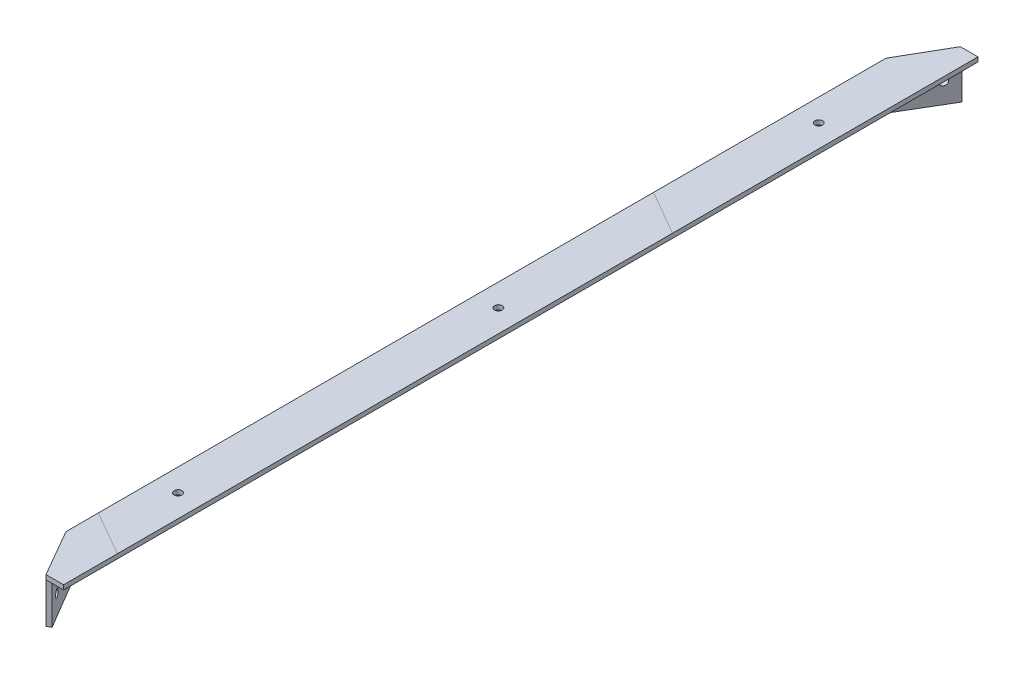
SolidWorks part; units mm, degrees
material "1.0116 (S235J2G3)"
ref_plane "Front Plane" through (0, 0, 0) normal (0, 0, 1) x (1, 0, 0)
ref_plane "Top Plane" through (0, 0, 0) normal (0, 1, 0) x (1, 0, 0)
ref_plane "Right Plane" through (0, 0, 0) normal (1, 0, 0) x (0, 0, -1)
sketch "Sketch1" plane through (0, 0, 0) normal (0, 0, 1) x (1, 0, 0)
  line L6 (0, 0) -> (0, 70)
  line L7 (0, 70) -> (70, 70)
  line L8 (70, 70) -> (70, 63)
  line L9 (70, 63) -> (7, 63)
  line L10 (7, 63) -> (7, 0)
  line L11 (7, 0) -> (0, 0)
  dimension "D1" = 70
  dimension "D2" = 70
  dimension "D3" = 7
  dimension "D4" = 7
extrude "Boss-Extrude1" add sketch "Sketch1" along normal blind 640
sketch "Sketch21" plane through (0, 0, 0) normal (0, 0, -1) x (-1, 0, 0)
  line L0 (0, 70) -> (-70, 70) construction
  line L1 (-70, 70) -> (-70, 0) construction
  line L2 (-70, 0) -> (0, 0) construction
  line L3 (0, 0) -> (0, 69.2595) construction
sketch "Sketch22" plane through (0, 70, 0) normal (0, 1, 0) x (1, 0, 0)
  line L0 (70, 0) -> (0, 0) construction
  line L1 (0, -55) -> (0, 55) construction
  circle A0 centre (35, 0) radius 6
  circle A1 centre (35, 500) radius 6
  circle A2 centre (35, -500) radius 6
  dimension "D1" = 12
  dimension "D2" = 12
  dimension "D3" = 12
  dimension "D4" = 500
  dimension "D5" = 500
  dimension "D6" = 35
  dimension "D7" = 35
extrude "Cut-Extrude4" cut sketch "Sketch22" against normal blind 10
sketch "Sketch23" plane through (0, 0, 0) normal (0, 1, 0) x (1, 0, 0)
  line L0 (0, -640) -> (42.5, -713.6122)
  line L1 (42.5, -713.6122) -> (48.5622, -710.1122)
  line L2 (48.5622, -710.1122) -> (7, -640)
  line L3 (7, -640) -> (0, -640)
  line L4 (0, -55) -> (0, 55) construction
  dimension "D1" = 7
  dimension "D2" = 210
  dimension "D3" = 85
extrude "Boss-Extrude2" add sketch "Sketch23" along normal blind 63
sketch "Sketch25" plane through (0, 63, 0) normal (0, 1, 0) x (1, 0, 0)
  line L0 (70, -640) -> (0, -640)
  line L1 (70, -640) -> (70, 0) construction
  line L2 (7, -640) -> (70, -640) construction
  line L3 (0, -640) -> (42.5, -713.6122) construction
  line L4 (0, -640) -> (42.5, -713.6122)
  line L5 (42.5, -713.6122) -> (48.5622, -710.1122) construction
  line L6 (42.5, -713.6122) -> (70, -713.6122)
  line L7 (70, -713.6122) -> (70, -640)
extrude "Boss-Extrude3" add sketch "Sketch25" along normal blind 7
sketch "Sketch26" plane through (-275.5567, 0, 163.3488) normal (0.8602, 0, -0.5099) x (-0.5099, 0, -0.8602)
  line L0 (-635.6125, 0) -> (-554.1071, 0) construction
  line L1 (-635.6125, 63) -> (-635.6125, 0) construction
  line L2 (-554.1071, 0) -> (-554.1071, 63) construction
  circle A0 centre (-614.3625, 31.5) radius 6
  circle A1 centre (-575.3671, 31.5) radius 6
  dimension "D1" = 12
  dimension "D2" = 12
  dimension "D3" = 31.5
  dimension "D4" = 31.5
  dimension "D5" = 21.25
  dimension "D6" = 21.26
extrude "Cut-Extrude5" cut sketch "Sketch26" against normal blind 7
mirror "Mirror1" about plane through (0, 0, 0) normal (0, 0, 1) of bodies 114 116
fillet "Fillet1" radius 10 2 edges at (0, 35, -640) (0, 35, 640)
fillet "Fillet2" radius 10 2 edges at (7, 31.5, 640) (7, 31.5, -640)
sketch "Sketch27" plane through (0, 70, 0) normal (0, 1, 0) x (1, 0, 0)
  line L0 (0, -589.3476) -> (70, -629.7622)
  line L1 (0, -38.5) -> (0, 38.5) construction
  line L2 (70, -713.6122) -> (70, 713.6122) construction
  line L3 (70, -629.7622) -> (70, 236.7622)
  line L4 (70, 236.7622) -> (0, 277.1767)
  line L5 (0, 277.1767) -> (0, -589.3476)
  line L6 (42.5, -713.6122) -> (70, -713.6122) construction
  dimension "D1" = 60
  dimension "D2" = 60
  dimension "D3" = 83.85
  dimension "D4" = 476.85
split line "Split Line1"
fillet "Fillet3" radius 5 5 edges at (28.48, 63, 676.2351) (7.3558, 63, 639.9025) (28.48, 63, -676.2351) (7.3558, 63, -639.9025) (7, 63, 0)
